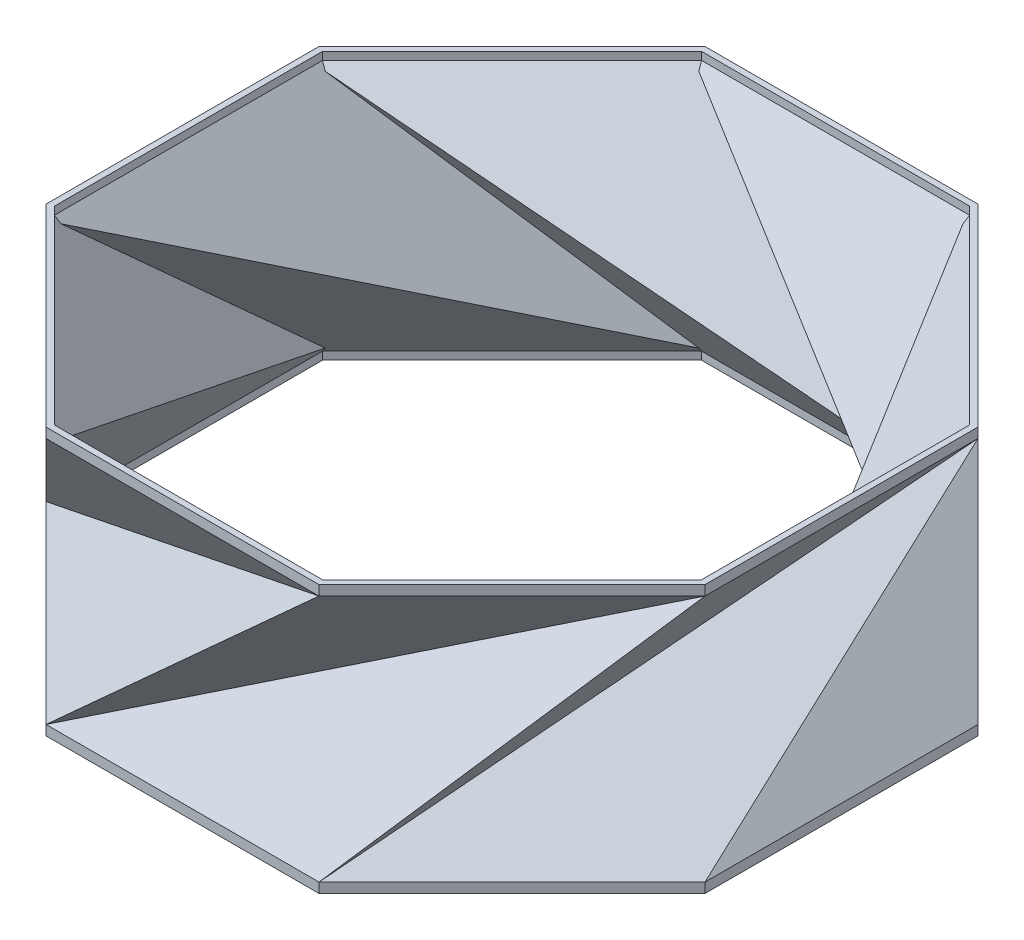
SolidWorks part; units mm, degrees
ref_plane "정면" through (0, 0, 0) normal (0, 0, 1) x (1, 0, 0)
ref_plane "윗면" through (0, 0, 0) normal (0, 1, 0) x (1, 0, 0)
ref_plane "우측면" through (0, 0, 0) normal (1, 0, 0) x (0, 0, -1)
sketch "스케치1" plane through (0, 0, 0) normal (0, 1, 0) x (1, 0, 0)
  line L0 (-55, 0) -> (55, 0) construction
  line L1 (33.2597, -13.7766) -> (33.2597, 13.7766)
  line L2 (33.2597, 13.7766) -> (13.7766, 33.2597)
  line L3 (13.7766, 33.2597) -> (-13.7766, 33.2597)
  line L4 (-13.7766, 33.2597) -> (-33.2597, 13.7766)
  line L5 (-33.2597, 13.7766) -> (-33.2597, -13.7766)
  line L6 (-33.2597, -13.7766) -> (-13.7766, -33.2597)
  line L7 (-13.7766, -33.2597) -> (13.7766, -33.2597)
  line L8 (13.7766, -33.2597) -> (33.2597, -13.7766)
  circle A0 centre (0, 0) radius 36 construction
  dimension "D1" = 72
extrude "보스-돌출1" add sketch "스케치1" along normal blind 25
ref_plane "평면1" through (0, 16.126, 20.6923) normal (0, -0.6147, -0.7888) x (-1, 0, 0)
sketch "스케치2" plane through (0, 16.126, 20.6923) normal (0, -0.6147, -0.7888) x (-1, 0, 0)
  line L0 (13.7766, -20.4447) -> (-33.2597, 11.2506)
  line L1 (-33.2597, 11.2506) -> (-13.7766, -20.4447)
sketch "스케치3" plane through (0, 0, 33.2597) normal (0, 0, 1) x (1, 0, 0)
  line L0 (-13.7766, 0) -> (13.7766, 25)
  line L1 (13.7766, 25) -> (13.7766, 0) construction
  line L2 (-13.7766, 25) -> (13.7766, 25) construction
ref_plane "평면2" through (-13.7766, 0, 33.2597) normal (0.8293, 0.4408, -0.3435) x (0.543, -0.781, 0.3087)
sketch "스케치4" plane through (-13.7766, 0, 33.2597) normal (0.8293, 0.4408, -0.3435) x (0.543, -0.781, 0.3087)
  line L0 (0, 0) -> (14.9601, -3.6426) construction
  line L1 (0, 0) -> (-4.5641, -14.7052) construction
  line L2 (0, 0) -> (14.9601, -3.6426)
  line L3 (0, 0) -> (-4.5641, -14.7052)
  line L4 (14.9601, -3.6426) -> (-4.5641, -14.7052)
extrude "컷-돌출1" cut sketch "스케치4" along normal up to vertex (56.7186 mm away) up to point (33.2597, 25, 13.7766)
pattern_circular "원형 패턴4" count 8 over 360 about axis through (0, 0, 0) along (0, -1, 0) of "컷-돌출1"
sketch "스케치5" plane through (0, 0, 0) normal (0, -1, 0) x (1, 0, 0)
  line L8 (33.2597, 13.7766) -> (13.7766, 33.2597)
  line L9 (13.7766, 33.2597) -> (-13.7766, 33.2597)
  line L10 (33.2597, 13.7766) -> (13.7766, 33.2597)
  line L11 (-13.7766, 33.2597) -> (-33.2597, 13.7766)
  line L12 (-13.7766, 33.2597) -> (-33.2597, 13.7766)
  line L13 (-33.2597, 13.7766) -> (-33.2597, -13.7766)
  line L14 (-33.2597, 13.7766) -> (-33.2597, -13.7766)
  line L15 (-33.2597, -13.7766) -> (-13.7766, -33.2597)
  line L17 (13.7766, 33.2597) -> (-13.7766, 33.2597)
  line L24 (-33.2597, -13.7766) -> (-13.7766, -33.2597)
  line L25 (-13.7766, -33.2597) -> (13.7766, -33.2597)
  line L26 (-13.7766, -33.2597) -> (13.7766, -33.2597)
  line L27 (13.7766, -33.2597) -> (33.2597, -13.7766)
  line L28 (13.7766, -33.2597) -> (33.2597, -13.7766)
  line L29 (33.2597, -13.7766) -> (33.2597, 13.7766)
  line L30 (33.2597, -13.7766) -> (33.2597, 13.7766)
  dimension "D1" = 0
extrude "보스-돌출2" add sketch "스케치5" along normal blind 1
sketch "스케치6" plane through (0, 25, 0) normal (0, 1, 0) x (1, 0, 0)
  line L8 (13.7766, -33.2597) -> (33.2597, -13.7766)
  line L9 (33.2597, -13.7766) -> (33.2597, 13.7766)
  line L10 (33.2597, -13.7766) -> (33.2597, 13.7766)
  line L11 (33.2597, 13.7766) -> (13.7766, 33.2597)
  line L12 (33.2597, 13.7766) -> (13.7766, 33.2597)
  line L13 (13.7766, 33.2597) -> (-13.7766, 33.2597)
  line L14 (13.7766, 33.2597) -> (-13.7766, 33.2597)
  line L15 (-13.7766, 33.2597) -> (-33.2597, 13.7766)
  line L16 (13.7766, -33.2597) -> (33.2597, -13.7766)
  line L24 (-13.7766, 33.2597) -> (-33.2597, 13.7766)
  line L25 (-33.2597, 13.7766) -> (-33.2597, -13.7766)
  line L26 (-33.2597, 13.7766) -> (-33.2597, -13.7766)
  line L27 (-33.2597, -13.7766) -> (-13.7766, -33.2597)
  line L28 (-33.2597, -13.7766) -> (-13.7766, -33.2597)
  line L29 (-13.7766, -33.2597) -> (13.7766, -33.2597)
  line L30 (-13.7766, -33.2597) -> (13.7766, -33.2597)
  dimension "D1" = 0
extrude "보스-돌출3" add sketch "스케치6" along normal blind 1
shell "쉘1" thickness 0.6 removed face at (0, -1, 0) removed face at (0, 26, 0)
